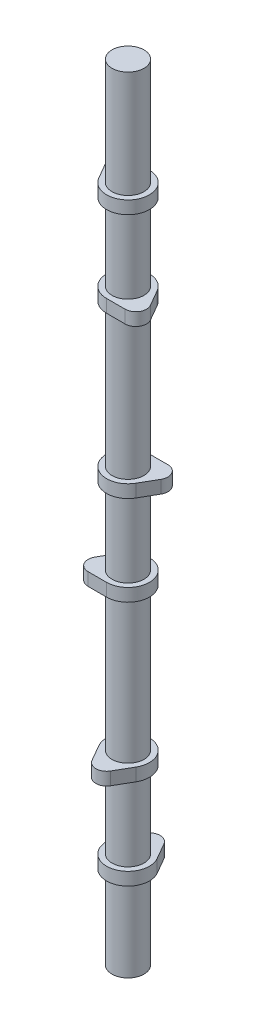
SolidWorks part; units mm, degrees
ref_plane "Front Plane" through (0, 0, 0) normal (0, 0, 1) x (1, 0, 0)
ref_plane "Top Plane" through (0, 0, 0) normal (0, 1, 0) x (1, 0, 0)
ref_plane "Right Plane" through (0, 0, 0) normal (1, 0, 0) x (0, 0, -1)
sketch "Sketch4" plane through (0, 0, 0) normal (0, 1, 0) x (1, 0, 0)
  line L0 (5.4993, 15.875) -> (10.9985, 6.35)
  line L1 (-5.4993, 15.875) -> (-10.9985, 6.35)
  arc A0 (-10.9985, 6.35) -> (10.9985, 6.35) centre (0, 0) ccw
  arc A1 (5.4993, 15.875) -> (-5.4993, 15.875) centre (0, 12.7) ccw
  dimension "D1" = 25.4
  dimension "D2" = 12.7
  dimension "D3" = 12.7
extrude "Boss-Extrude2" add sketch "Sketch4" along normal mid plane 7.62
ref_axis "Axis2" through (0, 143.9241, 0) along (0, -1, 0)
pattern_linear "LPattern4" count 2 spacing 53.34 along (0, 1, 0) of bodies 114
move or copy body "Body-Move/Copy5" bodies to move or copy 115 copy no rotation origin (0, 0, 0) rotation axis (0, 1, 0) rotation angle 180
pattern_linear "LPattern5" count 3 spacing 146.05 along (0, 1, 0) of bodies 114 116
move or copy body "Body-Move/Copy6" bodies to move or copy 117 119 copy no rotation origin (0, 0, 0) rotation axis (0, 1, 0) rotation angle 120
move or copy body "Body-Move/Copy7" bodies to move or copy 118 120 copy no rotation origin (0, 0, 0) rotation axis (0, -1, 0) rotation angle 120
sketch "Sketch5" plane through (0, 0, 0) normal (0, 1, 0) x (1, 0, 0)
  circle A0 centre (0, 0) radius 9.5
  dimension "D1" = 19
extrude "Boss-Extrude3" add sketch "Sketch5" along normal blind 466.09 from offset 53.34 offset against normal yes
